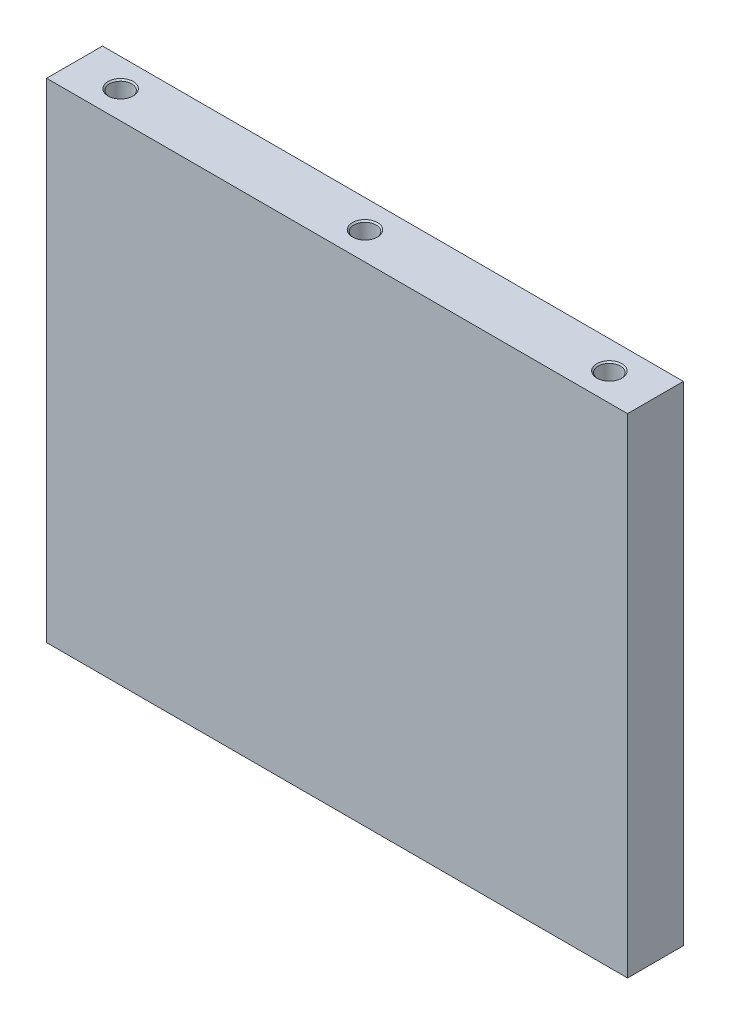
SolidWorks part; units mm, degrees
ref_plane "Front Plane" through (0, 0, 0) normal (0, 0, 1) x (1, 0, 0)
ref_plane "Top Plane" through (0, 0, 0) normal (0, 1, 0) x (1, 0, 0)
ref_plane "Right Plane" through (0, 0, 0) normal (1, 0, 0) x (0, 0, -1)
sketch "Sketch1" plane through (0, 0, -58) normal (0, 1, 0) x (1, 0, 0)
  line L1 (-104, -68) -> (104, -68)
  line L2 (-104, -68) -> (-104, -48)
  line L3 (-104, -48) -> (104, -48)
  line L4 (104, -68) -> (104, -48)
  line L5 (0, -69) -> (0, -47) construction
  line L6 (-96.25, -58) -> (96.25, -58) construction
  point P4 (-66.5242, -95.9873)
  point P5 (0, -68)
  point P8 (-104, -58)
  dimension "D1" = 208
  dimension "D2" = 20
extrude "Boss-Extrude1" add sketch "Sketch1" along normal blind 175
sketch "Sketch2" plane through (0, 175, 0) normal (0, 1, 0) x (1, 0, 0)
  line L0 (0, 0) -> (0, -51.17) construction
  circle A0 centre (0, 0) radius 4
  circle A1 centre (-87.5, 0) radius 4
  circle A2 centre (87.5, 0) radius 4
  point P8 (-87.5, 49.3807)
  dimension "D1" = 8
  dimension "D2" = 175
  dimension "D3" = 167
extrude "Cut-Extrude1" cut sketch "Sketch2" against normal blind 12
ref_plane "Plane1" through (0, 87.5, 0) normal (0, 1, 0) x (1, 0, 0)
mirror "Mirror6" about plane through (0, 87.5, 0) normal (0, 1, 0) of "Cut-Extrude1"
chamfer "Chamfer1" distance 0.5 angle 45 6 edges at (87.5, 175, -4) (0, 175, 4) (-87.5, 175, 4) (-87.5, 0, 4) (0, 0, 4) (87.5, 0, -4)
